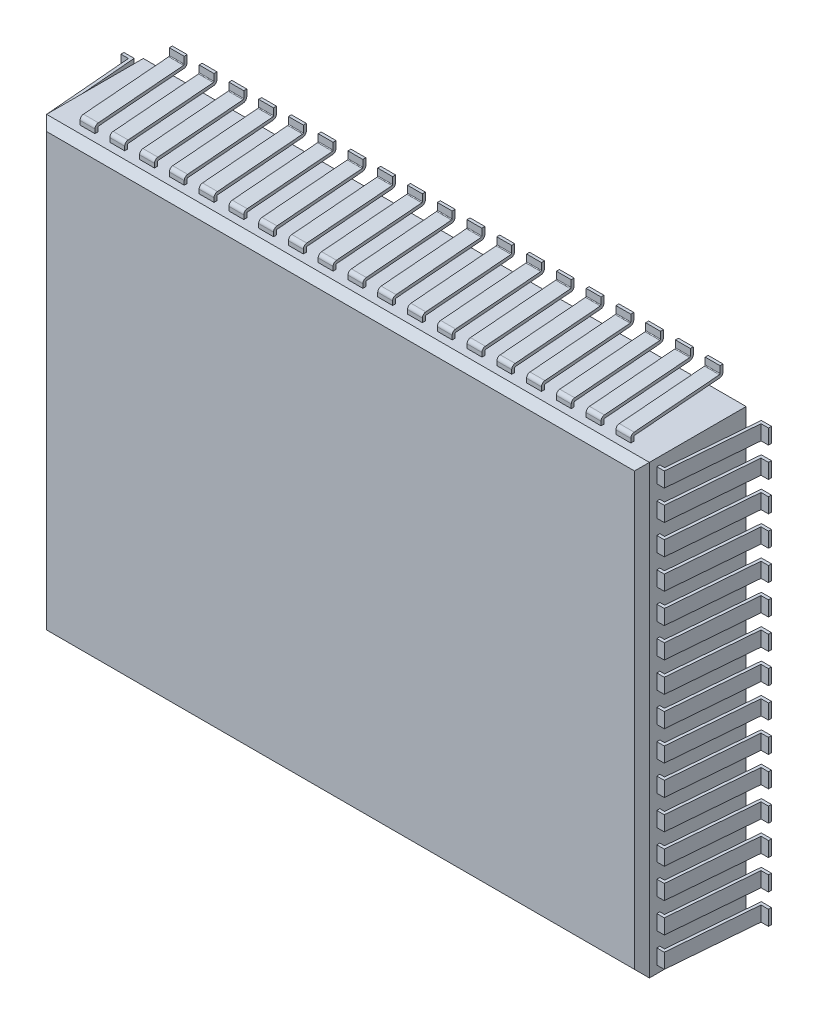
SolidWorks part; units mm, degrees
material "ABS"
ref_plane "Front" through (0, 0, 0) normal (0, 0, 1) x (1, 0, 0)
ref_plane "Top" through (0, 0, 0) normal (0, 1, 0) x (1, 0, 0)
ref_plane "Right" through (0, 0, 0) normal (1, 0, 0) x (0, 0, -1)
sketch "COMPONENT_OUTLINE" plane through (0, 0, 0) normal (0, 0, 1) x (1, 0, 0)
  line L0 (-4.05, 3) -> (-4.05, -3)
  line L1 (-4.05, -3) -> (4.05, -3)
  line L2 (4.05, -3) -> (4.05, 3)
  line L3 (4.05, 3) -> (-4.05, 3)
  line L4 (4.05, -3) -> (-4.05, 3) construction
  line L5 (-4.05, -3) -> (4.05, 3) construction
  dimension "D1" = 6
  dimension "D2" = 8.1
extrude "Extrude1" add sketch "COMPONENT_OUTLINE" along normal blind 1.4
sketch "Sketch1" plane through (0, 0, 0) normal (1, 0, 0) x (0, 0, -1)
  line L0 (-1.2, 3) -> (-1.2, 3.1)
  line L1 (-1.4, 3) -> (0, 3) construction
  line L2 (-1.2, 3.1) -> (0, 3.2)
  line L3 (0, 3.2) -> (0, 3.3)
  dimension "D1" = 0.1
  dimension "D2" = 0.2
  dimension "D3" = 0.2
  dimension "D4" = 0.1
extrude "Extrude-Thin1" add sketch "Sketch1" along normal mid plane 0.2 thin thin type one direction wall 0.04
pattern_linear "LPattern1" count 10 spacing 0.4 along (-1, 0, 0) count 10 spacing 0.4 along (1, 0, 0) of "Extrude-Thin1"
mirror "Mirror1" about plane through (0, 0, 0) normal (0, 1, 0) of "Extrude-Thin1", "LPattern1"
sketch "Sketch2" plane through (0, 0, 0) normal (0, 1, 0) x (1, 0, 0)
  line L0 (4.05, -1.2) -> (4.15, -1.2)
  line L1 (4.05, -1.4) -> (4.05, 0) construction
  line L2 (4.15, -1.2) -> (4.25, 0)
  line L3 (4.25, 0) -> (4.35, 0)
  line L4 (4.05, -1.4) -> (-4.05, -1.4) construction
  dimension "D1" = 0.1
  dimension "D2" = 0.2
  dimension "D3" = 0.2
  dimension "D4" = 0.1
extrude "Extrude-Thin2" add sketch "Sketch2" along normal mid plane 0.2 thin thin type one direction reverse wall 0.04
pattern_linear "LPattern2" count 8 spacing 0.4 along (0, 1, 0) count 8 spacing 0.4 along (0, -1, 0) of "Extrude-Thin2"
mirror "Mirror2" about plane through (0, 0, 0) normal (1, 0, 0) of "LPattern2"
chamfer "Chamfer1" distance 0.1 angle 45 4 edges at (4.05, 0, 1.4) (0, -3, 1.4) (-4.05, 0, 1.4) (0, 3, 1.4)
